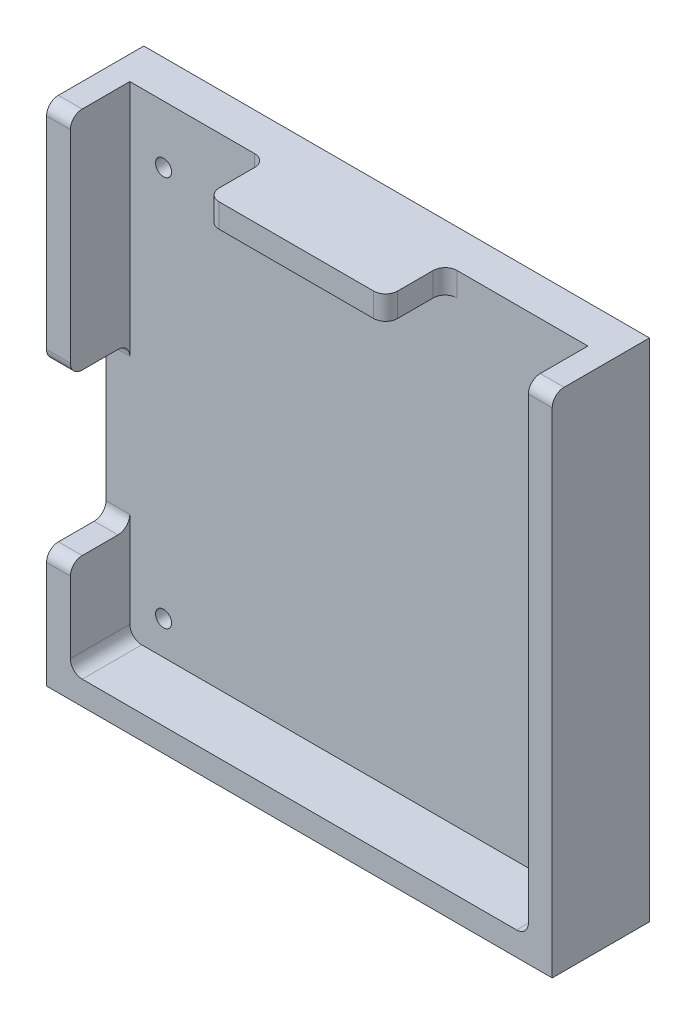
SolidWorks part; units mm, degrees
ref_plane "Front Plane" through (0, 0, 0) normal (0, 0, 1) x (1, 0, 0)
ref_plane "Top Plane" through (0, 0, 0) normal (0, 1, 0) x (1, 0, 0)
ref_plane "Right Plane" through (0, 0, 0) normal (1, 0, 0) x (0, 0, -1)
sketch "Sketch1" plane through (0, 0, 0) normal (0, 0, 1) x (1, 0, 0)
  line L0 (0, 0) -> (0, 42.5) construction
  line L1 (-42.5, 42.5) -> (42.5, 42.5)
  line L2 (-42.5, 42.5) -> (-42.5, -42.5)
  line L3 (-42.5, -42.5) -> (42.5, -42.5)
  line L4 (42.5, 42.5) -> (42.5, -42.5)
  line L5 (-42.5, 42.5) -> (42.5, -42.5) construction
  line L6 (-42.5, -42.5) -> (42.5, 42.5) construction
  line L7 (0, 0) -> (42.5, 0) construction
  circle A0 centre (-32.83, 32.83) radius 1.35
  circle A1 centre (-32.83, -32.83) radius 1.35
  circle A2 centre (32.83, 32.83) radius 1.35
  circle A3 centre (32.83, -32.83) radius 1.35
  point P0 (0, 0)
  point P16 (0, 0)
  point P18 (0, 0)
  point P19 (0, 0)
  dimension "D5" = 2.7
  dimension "D1" = 85
  dimension "D2" = 85
  dimension "D3" = 65.66
  dimension "D4" = 65.66
extrude "Boss-Extrude1" add sketch "Sketch1" along normal blind 6.35
sketch "Sketch2" plane through (0, 0, 6.35) normal (0, 0, 1) x (1, 0, 0)
  line L0 (42.5, 42.5) -> (-42.5, 42.5) construction
  line L1 (-42.5, 42.5) -> (-38.5, 42.5)
  line L2 (-42.5, 42.5) -> (-42.5, 4.5)
  line L3 (-42.5, 4.5) -> (-38.5, 4.5)
  line L4 (-38.5, 42.5) -> (-38.5, 4.5)
  line L5 (-42.5, -42.5) -> (-38.5, -42.5)
  line L6 (-42.5, -42.5) -> (-42.5, -22.5)
  line L7 (-42.5, -22.5) -> (-38.5, -22.5)
  line L8 (-38.5, -42.5) -> (-38.5, -22.5)
  line L9 (-38.5, -38.5) -> (42.5, -38.5)
  line L10 (-38.5, -38.5) -> (-38.5, -42.5)
  line L11 (-38.5, -42.5) -> (42.5, -42.5)
  line L12 (42.5, -38.5) -> (42.5, -42.5)
  line L13 (42.5, -42.5) -> (38.5, -42.5)
  line L14 (42.5, -42.5) -> (42.5, 42.5)
  line L15 (42.5, 42.5) -> (38.5, 42.5)
  line L16 (38.5, -42.5) -> (38.5, 42.5)
  line L18 (-15.5, 42.5) -> (14.5, 42.5)
  line L19 (-15.5, 42.5) -> (-15.5, 38.5)
  line L20 (-15.5, 38.5) -> (14.5, 38.5)
  line L21 (14.5, 42.5) -> (14.5, 38.5)
  line M13 (42.5, -42.5) -> (42.5, 42.5)
  line M14 (42.5, 42.5) -> (-42.5, 42.5)
  line M15 (-42.5, 42.5) -> (-42.5, -42.5)
  line M16 (-42.5, -42.5) -> (42.5, -42.5)
  dimension "D1" = 30
  dimension "D2" = 4
  dimension "D3" = 4
  dimension "D4" = 4
  dimension "D5" = 4
  dimension "D6" = 38
  dimension "D7" = 20
  dimension "D8" = 4
  dimension "D9" = 23
extrude "Boss-Extrude3" add sketch "Sketch2" along normal blind 10 contours L4 L3 M14 M15 | L8 L7 M16 M15 | L16 L9 L8 M16 | L16 L9 M13 M14 | L21 L19 L20 M14 | L16 L11 L9 M13 region at (-40.5, 23.5, 6.35) region at (-0.5, 40.5, 6.35) region at (-40.5, -32.5, 6.35) region at (40.5, 2, 6.35) region at (0, -40.5, 6.35) region at (40.5, -40.5, 6.35)
fillet "Fillet1" radius 2 12 edges at (-40.5, -22.5, 16.35) (-40.5, 4.5, 16.35) (-40.5, 42.5, 16.35) (40.5, 42.5, 16.35) (14.5, 40.5, 16.35) (-15.5, 40.5, 16.35) (-38.5, -38.5, 11.35) (38.5, -38.5, 11.35) (14.5, 40.5, 6.35) (-15.5, 40.5, 6.35) (-40.5, -22.5, 6.35) (-40.5, 4.5, 6.35)
